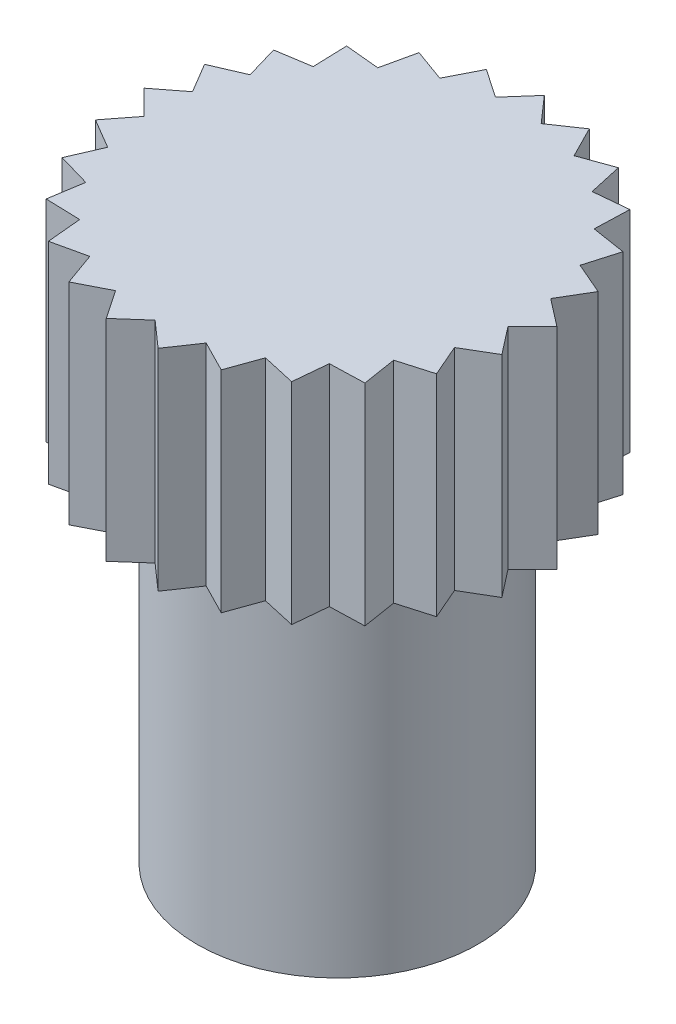
SolidWorks part; units mm, degrees
ref_plane "Front Plane" through (0, 0, 0) normal (0, 0, 1) x (1, 0, 0)
ref_plane "Top Plane" through (0, 0, 0) normal (0, 1, 0) x (1, 0, 0)
ref_plane "Right Plane" through (0, 0, 0) normal (1, 0, 0) x (0, 0, -1)
sketch "Sketch1" plane through (0, 0, 0) normal (0, 1, 0) x (1, 0, 0)
  circle A0 centre (0, 0) radius 2
extrude "Boss-Extrude1" add sketch "Sketch1" along normal blind 5.01
sketch "Sketch4" plane through (0, 5.01, 0) normal (0, 1, 0) x (1, 0, 0)
  line L0 (0, 0) -> (0, 2.95) construction
  line L1 (0, 0) -> (0.3697, 2.9267) construction
  line L2 (0, 0) -> (0.7336, 2.8573) construction
  line L3 (0, 0) -> (1.086, 2.7428) construction
  line L4 (0, 0) -> (1.4212, 2.5851) construction
  line L5 (0, 0) -> (1.734, 2.3866) construction
  line L6 (0, 0) -> (2.0194, 2.1505) construction
  line L7 (0, 0) -> (2.273, 1.8804) construction
  line L8 (0, 0) -> (2.4908, 1.5807) construction
  line L9 (0, 0) -> (2.6692, 1.256) construction
  line L10 (0, 0) -> (2.8056, 0.9116) construction
  line L11 (0, 0) -> (2.8977, 0.5528) construction
  line L12 (0, 0) -> (2.9442, 0.1852) construction
  line L13 (0, 0) -> (2.9442, -0.1852) construction
  line L14 (0, 0) -> (2.8977, -0.5528) construction
  line L15 (0, 0) -> (2.8056, -0.9116) construction
  line L16 (0, 0) -> (2.6692, -1.256) construction
  line L17 (0, 0) -> (2.4908, -1.5807) construction
  line L18 (0, 0) -> (2.273, -1.8804) construction
  line L19 (0, 0) -> (2.0194, -2.1505) construction
  line L20 (0, 0) -> (1.734, -2.3866) construction
  line L21 (0, 0) -> (1.4212, -2.5851) construction
  line L22 (0, 0) -> (1.086, -2.7428) construction
  line L23 (0, 0) -> (0.7336, -2.8573) construction
  line L24 (0, 0) -> (0.3697, -2.9267) construction
  line L25 (0, 0) -> (0, -2.95) construction
  line L26 (0, 0) -> (-0.3697, -2.9267) construction
  line L27 (0, 0) -> (-0.7336, -2.8573) construction
  line L28 (0, 0) -> (-1.086, -2.7428) construction
  line L29 (0, 0) -> (-1.4212, -2.5851) construction
  line L30 (0, 0) -> (-1.734, -2.3866) construction
  line L31 (0, 0) -> (-2.0194, -2.1505) construction
  line L32 (0, 0) -> (-2.273, -1.8804) construction
  line L33 (0, 0) -> (-2.4908, -1.5807) construction
  line L34 (0, 0) -> (-2.6692, -1.256) construction
  line L35 (0, 0) -> (-2.8056, -0.9116) construction
  line L36 (0, 0) -> (-2.8977, -0.5528) construction
  line L37 (0, 0) -> (-2.9442, -0.1852) construction
  line L38 (0, 0) -> (-2.9442, 0.1852) construction
  line L39 (0, 0) -> (-2.8977, 0.5528) construction
  line L40 (0, 0) -> (-2.8056, 0.9116) construction
  line L41 (0, 0) -> (-2.6692, 1.256) construction
  line L42 (0, 0) -> (-2.4908, 1.5807) construction
  line L43 (0, 0) -> (-2.273, 1.8804) construction
  line L44 (0, 0) -> (-2.0194, 2.1505) construction
  line L45 (0, 0) -> (-1.734, 2.3866) construction
  line L46 (0, 0) -> (-1.4212, 2.5851) construction
  line L47 (0, 0) -> (-1.086, 2.7428) construction
  line L48 (0, 0) -> (-0.7336, 2.8573) construction
  line L49 (0, 0) -> (-0.3697, 2.9267) construction
  line L50 (0, 2.95) -> (0.3259, 2.5795)
  line L51 (0.3259, 2.5795) -> (0.7336, 2.8573)
  line L52 (0.7336, 2.8573) -> (0.9571, 2.4174)
  line L53 (0.9571, 2.4174) -> (1.4212, 2.5851)
  line L54 (1.4212, 2.5851) -> (1.5282, 2.1034)
  line L55 (1.5282, 2.1034) -> (2.0194, 2.1505)
  line L56 (2.0194, 2.1505) -> (2.0033, 1.6573)
  line L57 (2.0033, 1.6573) -> (2.4908, 1.5807)
  line L58 (2.4908, 1.5807) -> (2.3526, 1.107)
  line L59 (2.3526, 1.107) -> (2.8056, 0.9116)
  line L60 (2.8056, 0.9116) -> (2.5539, 0.4872)
  line L61 (2.5539, 0.4872) -> (2.9442, 0.1852)
  line L62 (2.9442, 0.1852) -> (2.5949, -0.1633)
  line L63 (2.5949, -0.1633) -> (2.8977, -0.5528)
  line L64 (2.8977, -0.5528) -> (2.4727, -0.8034)
  line L65 (2.4727, -0.8034) -> (2.6692, -1.256)
  line L66 (2.6692, -1.256) -> (2.1953, -1.3931)
  line L67 (2.1953, -1.3931) -> (2.273, -1.8804)
  line L68 (2.273, -1.8804) -> (1.7798, -1.8953)
  line L69 (1.7798, -1.8953) -> (1.734, -2.3866)
  line L70 (1.734, -2.3866) -> (1.2526, -2.2784)
  line L71 (1.2526, -2.2784) -> (1.086, -2.7428)
  line L72 (1.086, -2.7428) -> (0.6466, -2.5183)
  line L73 (0.6466, -2.5183) -> (0.3697, -2.9267)
  line L74 (0.3697, -2.9267) -> (0, -2.6)
  line L75 (0, -2.6) -> (-0.3697, -2.9267)
  line L76 (-0.3697, -2.9267) -> (-0.6466, -2.5183)
  line L77 (-0.6466, -2.5183) -> (-1.086, -2.7428)
  line L78 (-1.086, -2.7428) -> (-1.2526, -2.2784)
  line L79 (-1.2526, -2.2784) -> (-1.734, -2.3866)
  line L80 (-1.734, -2.3866) -> (-1.7798, -1.8953)
  line L81 (-1.7798, -1.8953) -> (-2.273, -1.8804)
  line L82 (-2.273, -1.8804) -> (-2.1953, -1.3931)
  line L83 (-2.1953, -1.3931) -> (-2.6692, -1.256)
  line L84 (-2.6692, -1.256) -> (-2.4727, -0.8034)
  line L85 (-2.4727, -0.8034) -> (-2.8977, -0.5528)
  line L86 (-2.8977, -0.5528) -> (-2.5949, -0.1633)
  line L87 (-2.5949, -0.1633) -> (-2.9442, 0.1852)
  line L88 (-2.9442, 0.1852) -> (-2.5539, 0.4872)
  line L89 (-2.5539, 0.4872) -> (-2.8056, 0.9116)
  line L90 (-2.8056, 0.9116) -> (-2.3526, 1.107)
  line L91 (-2.3526, 1.107) -> (-2.4908, 1.5807)
  line L92 (-2.4908, 1.5807) -> (-2.0033, 1.6573)
  line L93 (-2.0033, 1.6573) -> (-2.0194, 2.1505)
  line L94 (-2.0194, 2.1505) -> (-1.5282, 2.1034)
  line L95 (-1.5282, 2.1034) -> (-1.4212, 2.5851)
  line L96 (-1.4212, 2.5851) -> (-0.9571, 2.4174)
  line L97 (-0.9571, 2.4174) -> (-0.7336, 2.8573)
  line L98 (-0.7336, 2.8573) -> (-0.3259, 2.5795)
  line L99 (-0.3259, 2.5795) -> (0, 2.95)
  circle A0 centre (0, 0) radius 2.95 construction
  circle A1 centre (0, 0) radius 2.6 construction
  point P56 (0, 0)
  point P130 (0, 0)
  circle M1 centre (0, 0) radius 2
  dimension "D1" = 25
  dimension "D2" = 50
extrude "Boss-Extrude2" add sketch "Sketch4" along normal blind 3 contours L99 L98 L97 L96 L95 L94 L93 L92 L91 L90 L89 L88 L87 L86 L85 L84 L83 L82 L81 L80 L79 L78 L77 L76 L75 L74 L73 L72 L71 L70 L69 L68 L67 L66 L65 L64 L63 L62 L61 L60 L59 L58 L57 L56 L55 L54 L53 L52 L51 L50 | M1 region at (0.1005, 5.01, -2.7098) region at (0, 5.01, 0)
